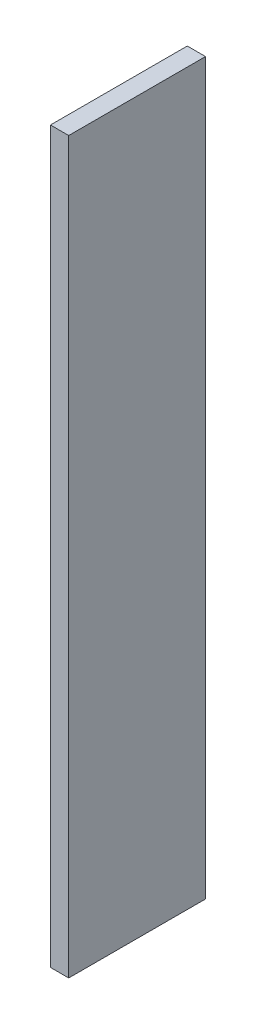
SolidWorks part; units mm, degrees
ref_plane "Front Plane" through (0, 0, 0) normal (0, 0, 1) x (1, 0, 0)
ref_plane "Top Plane" through (0, 0, 0) normal (0, 1, 0) x (1, 0, 0)
ref_plane "Right Plane" through (0, 0, 0) normal (1, 0, 0) x (0, 0, -1)
sketch "Sketch1" plane through (0, 0, 0) normal (0, 0, 1) x (1, 0, 0)
  line L1 (0, 0) -> (0.4, 0)
  line L2 (0, 0) -> (0, 16)
  line L3 (0, 16) -> (0.4, 16)
  line L4 (0.4, 0) -> (0.4, 16)
  dimension "D2" = 16
extrude "Boss-Extrude1" add sketch "Sketch1" along normal blind 3
equation "\"A.L\"= 0.06m"
equation "\"A.h\"= 0.005m"
equation "\"A.d\"= 0.003m"
equation "\"A.delta\"= 45.0001"
equation "\"A.w\"= 0.02m"
equation "\"A.v\"= 0.03m"
equation "\"A.s\"= 0.0075m"
equation "\"A.t\"= 0.005m"
equation "\"B.L\"= 0.04m"
equation "\"B.h\"= 0.004m"
equation "\"B.s\"= 0.008m"
equation "\"B.t\"= 0.004m"
equation "\"C.h\"= 0.0062m"
equation "\"C.d\"= 0.003m"
equation "\"C.L\"= 0.05m"
equation "\"C.wmax\"= 0.005m"
equation "\"D.L\"= 0.045m"
equation "\"D.h\"= 0.004m"
equation "\"D.s\"= 0.01m"
equation "\"D.t\"= 0.004m"
equation "\"a_h\"= 0.0001m"
equation "\"a_d\"= 0.003m"
equation "\"a_L\"= 0.01m"
equation "\"b_h\"= 0.0004m"
equation "\"b_d\"= 0.003m"
equation "\"b_L\"= 0.01m"
equation "\"c_h\"= 0.0001m"
equation "\"c_d\"= 0.003m"
equation "\"c_L\"= 0.01m"
equation "\"d_h\"= 0.0001m"
equation "\"d_d\"= 0.003m"
equation "\"d_L\"= 0.01m"
equation "\"S.h\"= 0.015m"
equation "\"S.L\"= 0.0559m"
equation "\"D1@Sketch1\"=\"b_h\""
equation "\"D2@Sketch1\"=\"b_L\"+0.006"
equation "\"D1@Boss-Extrude1\"=\"b_d\""
